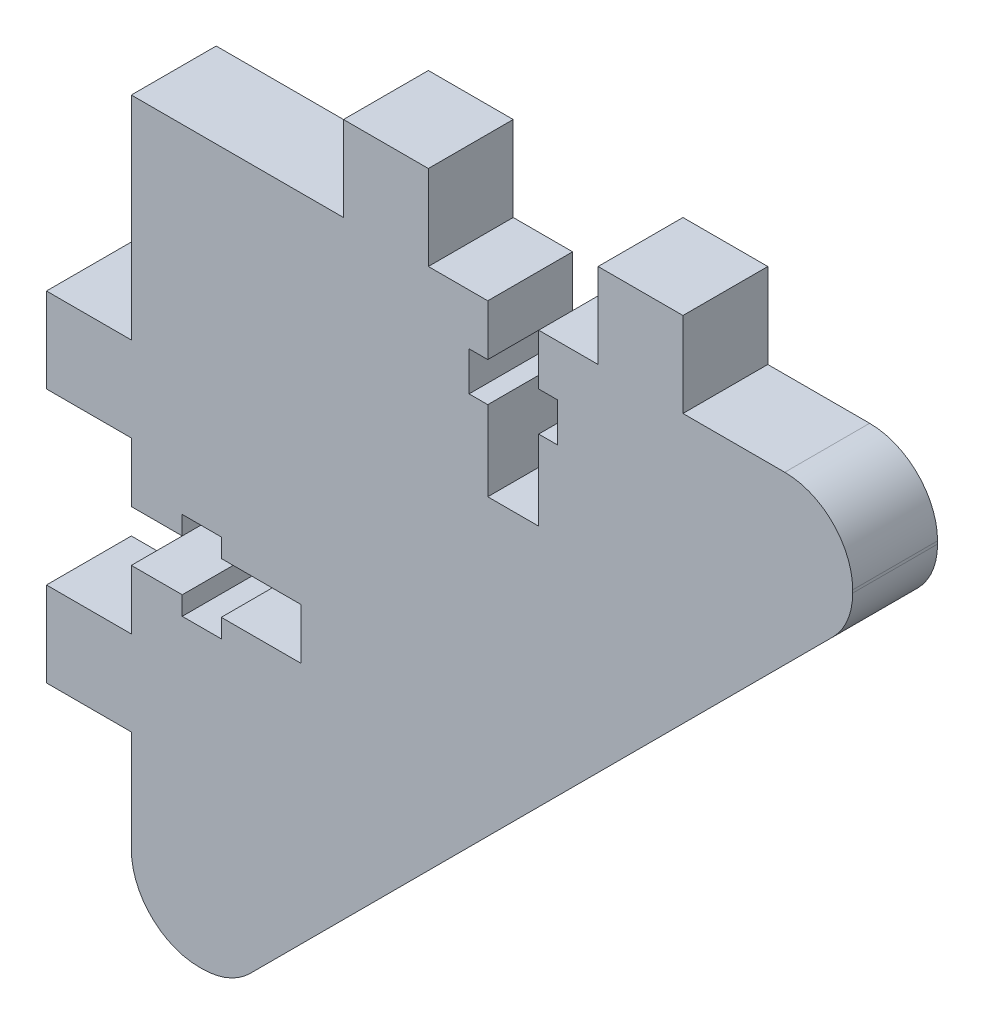
SolidWorks part; units mm, degrees
ref_plane "Front Plane" through (0, 0, 0) normal (0, 0, 1) x (1, 0, 0)
ref_plane "Top Plane" through (0, 0, 0) normal (0, 1, 0) x (1, 0, 0)
ref_plane "Right Plane" through (0, 0, 0) normal (1, 0, 0) x (0, 0, -1)
sketch "Sketch1" plane through (0, 0, 0) normal (0, 0, 1) x (1, 0, 0)
  line L0 (5, -5) -> (43.5, -5)
  line L1 (47.5, -9) -> (47.5, -9.1655)
  line L2 (46.3284, -11.9939) -> (11.9939, -46.3284)
  line L3 (9.1655, -47.5) -> (9, -47.5)
  line L4 (5, -43.5) -> (5, -5)
  line L5 (0, 18.5393) -> (0, -65.6726) construction
  line L6 (-18.1148, 0) -> (76.4115, 0) construction
  arc A2 (9, -47.5) -> (5, -43.5) centre (9, -43.5) cw
  arc A3 (11.9939, -46.3284) -> (9.1655, -47.5) centre (9.1655, -43.5) cw
  arc A4 (47.5, -9.1655) -> (46.3284, -11.9939) centre (43.5, -9.1655) cw
  arc A5 (47.5, -9) -> (43.5, -5) centre (43.5, -9) ccw
  line B0 (8, -24.9) -> (10.3, -24.9)
  line B1 (10.3, -29) -> (15, -29)
  line B2 (15, -26) -> (10.3, -26)
  line B3 (10.3, -24.9) -> (10.3, -26)
  line B4 (5, -27.5) -> (16.2208, -27.5) construction
  line B5 (5, -26) -> (5, -22.5)
  line B6 (0, -22.5) -> (0, -17.5)
  line B7 (0, -17.5) -> (5, -17.5)
  line B8 (0, -22.5) -> (5, -22.5)
  line B9 (5, -29) -> (5, -32.5)
  line B10 (5, -32.5) -> (0, -32.5)
  line B11 (0, -32.5) -> (0, -37.5)
  line B12 (0, -37.5) -> (5, -37.5)
  line B13 (5, -26) -> (5, -29) construction
  line B14 (5, -29) -> (8, -29)
  line B15 (10.3, -29) -> (10.3, -30.1)
  line B16 (8, -30.1) -> (8, -29)
  line B17 (15, -29) -> (15, -26)
  line B18 (8, -26) -> (8, -24.9)
  line B19 (10.3, -30.1) -> (8, -30.1)
  line B20 (8, -26) -> (5, -26)
  line B21 (15, -27.5) -> (5, -27.5) construction
  line B22 (30.1, -8) -> (30.1, -10.3)
  line B23 (26, -10.3) -> (26, -15)
  line B24 (29, -15) -> (29, -10.3)
  line B25 (30.1, -10.3) -> (29, -10.3)
  line B26 (27.5, -5) -> (27.5, -16.2208) construction
  line B27 (29, -5) -> (32.5, -5)
  line B28 (32.5, 0) -> (37.5, 0)
  line B29 (37.5, 0) -> (37.5, -5)
  line B30 (32.5, 0) -> (32.5, -5)
  line B31 (26, -5) -> (22.5, -5)
  line B32 (22.5, -5) -> (22.5, 0)
  line B33 (22.5, 0) -> (17.5, 0)
  line B34 (17.5, 0) -> (17.5, -5)
  line B35 (29, -5) -> (26, -5) construction
  line B36 (26, -5) -> (26, -8)
  line B37 (26, -10.3) -> (24.9, -10.3)
  line B38 (24.9, -8) -> (26, -8)
  line B39 (26, -15) -> (29, -15)
  line B40 (29, -8) -> (30.1, -8)
  line B41 (24.9, -10.3) -> (24.9, -8)
  line B42 (29, -8) -> (29, -5)
  line B43 (27.5, -15) -> (27.5, -5) construction
  dimension "D1" = 27.5
  dimension "D2" = 27.5
  dimension "D3" = 10
  dimension "D4" = 5
  dimension "D5" = 5
sketch_block_instance "Insert M3 plots ep 5mm-1"
sketch_block "Insert M3 plots ep 5mm" parameters "D1"=10, "D2"=5, "D3"=5
sketch_block_instance "Decoupe Insert M3-4"
sketch_block "Decoupe Insert M3" parameters "D1"=5.2, "D2"=3, "D3"=2.3, "D4"=3, "D5"=10
sketch_block_instance "Insert M3 plots ep 5mm-2"
extrude "Boss-Extrude1" add sketch "Sketch1" along normal blind 5 contours B42 B40 B22 B25 B24 B39 B23 B37 B41 B38 B36 L0 L4 B20 B18 B0 B3 B2 B17 B1 B15 B19 B16 B14 A2 L3 A3 L2 A4 L1 A5 | B6 B8 L4 B7 | B33 B34 L0 B32 | B28 B30 L0 B29 | B11 B12 L4 B10 region at (21.0021, -21.0021, 0) region at (20, -2.5, 0) region at (2.5, -20, 0) region at (35, -2.5, 0) region at (2.5, -35, 0)
